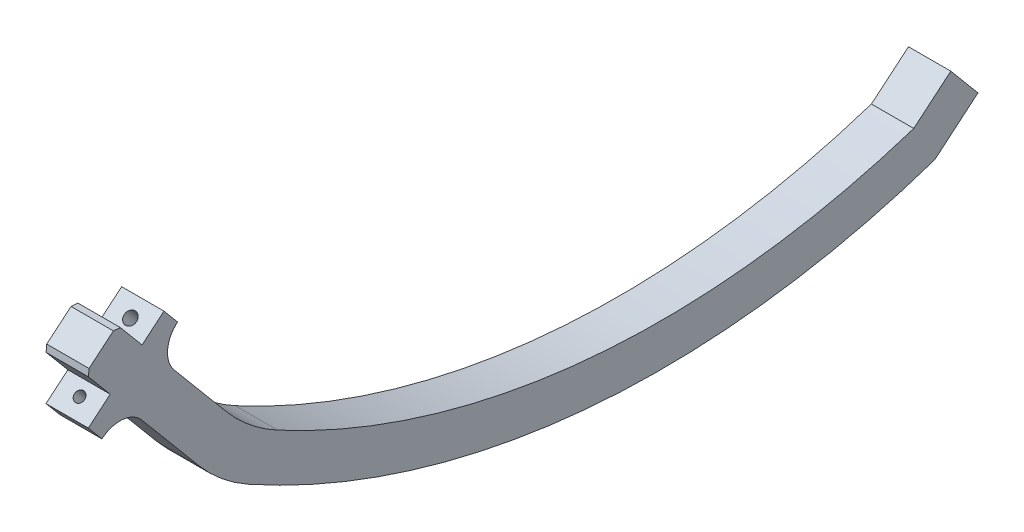
SolidWorks part; units mm, degrees
ref_plane "Ebene vorne" through (0, 0, 0) normal (0, 0, 1) x (1, 0, 0)
ref_plane "Ebene oben" through (0, 0, 0) normal (0, 1, 0) x (1, 0, 0)
ref_plane "Ebene rechts" through (0, 0, 0) normal (1, 0, 0) x (0, 0, -1)
sketch "Skizze1" plane through (0, 0, 0) normal (1, 0, 0) x (0, 0, -1)
  line L0 (0, 12) -> (-233.4212, 12) construction
  line L1 (-240, 65) -> (-230.7357, 72.7737)
  line L2 (0, 12) -> (-3.7358, 23.4037)
  line L3 (0, 12) -> (0, 39.1297) construction
  line L4 (0, 0) -> (-218.6687, 0) construction
  arc A0 (0, 12) -> (-240, 65) centre (-75.176, 241.4765) cw
  arc A1 (-3.7358, 23.4037) -> (-230.7357, 72.7737) centre (-75.176, 241.4765) cw
  dimension "D1" = 53
  dimension "D2" = 240
  dimension "D3" = 40
  dimension "D4" = 12
  dimension "D5" = 12
extrude "Aufsatz-Linear austragen1" add sketch "Skizze1" along normal blind 12
sketch "Skizze4" plane through (0, 0, 0) normal (1, 0, 0) x (0, 0, -1)
  line L0 (-230.7357, 72.7737) -> (-240, 65) construction
  line L2 (-3.7358, 23.4037) -> (6.769, 32.2183)
  line L3 (6.769, 32.2183) -> (14.4825, 23.0258)
  line L4 (14.4825, 23.0258) -> (2.2258, 12.7411)
  line L5 (-3.7358, 23.4037) -> (0, 12)
  arc A0 (0, 12) -> (2.2258, 12.7411) centre (-75.176, 241.4765) ccw
  arc A4 (-240, 65) -> (0, 12) centre (-75.176, 241.4765) ccw construction
  dimension "D1" = 16
  dimension "D2" = 12
extrude "Aufsatz-Linear austragen3" add sketch "Skizze4" along normal blind 12
sketch "Skizze5" plane through (12, 0, 0) normal (1, 0, 0) x (0, 0, -1)
  line L0 (-231.6625, 71.996) -> (-222.47, 79.7094)
  line L1 (-230.7357, 72.7737) -> (-232.109, 74.04) construction
  line L2 (-231.6625, 71.996) -> (-220.0923, 58.2072)
  line L3 (-230.7357, 72.7737) -> (-240, 65) construction
  line L4 (-222.47, 79.7094) -> (-210.8998, 65.9206)
  line L5 (-220.0923, 58.2072) -> (-192.9483, 44.5269)
  line L6 (-220.0923, 58.2072) -> (-211.3409, 65.5505) construction
  line L7 (-210.8998, 65.9206) -> (-192.9483, 44.5269)
  arc A6 (-230.7357, 72.7737) -> (-3.7358, 23.4037) centre (-75.176, 241.4765) ccw construction
  dimension "D1" = 12
  dimension "D2" = 1.2
  dimension "D3" = 18
extrude "Aufsatz-Linear austragen4" add sketch "Skizze5" against normal up to surface (12 mm away) up to face at (0, 27.4794, 77.4862)
sketch "Skizze6" plane through (12, 0, 0) normal (1, 0, 0) x (0, 0, -1)
  line L0 (-231.6625, 71.996) -> (-199.5106, 33.6789)
  line L1 (-199.5106, 33.6789) -> (-204.3677, 29.6033)
  line L2 (-204.3677, 29.6033) -> (-240, 65)
  line L3 (-240, 65) -> (-231.6625, 71.996)
extrude "Schnitt-Linear austragen1" cut sketch "Skizze6" against normal through all
sketch "Skizze7" plane through (12, 0, 0) normal (1, 0, 0) x (0, 0, -1)
  line L0 (-222.47, 79.7094) -> (-229.5406, 88.1359)
  line L1 (-192.9483, 44.5269) -> (-222.47, 79.7094) construction
  line L2 (-229.5406, 88.1359) -> (-238.7332, 80.4225)
  line L3 (-238.7332, 80.4225) -> (-231.6625, 71.996)
  line M4 (-222.47, 79.7094) -> (-231.6625, 71.996)
  dimension "D1" = 11
extrude "Aufsatz-Linear austragen5" [suppressed] add sketch "Skizze7" against normal up to surface (12 mm away) contours L2 L3 L0 M4
fillet "Verrundung1" radius 50 2 edges at (6, 35.2854, 200.8587) (6, 44.5269, 192.9483)
sketch "Skizze8" [suppressed] plane through (0, -76.6111, 91.3015) normal (0, 0.6428, -0.766) x (-1, 0, 0)
  line L0 (-6, 215.0619) -> (-6, 184.7045) construction
  line L1 (0, 215.0619) -> (-12, 215.0619) construction
  circle A0 centre (-6, 210.0619) radius 1.55
  dimension "D2" = 3.1
  dimension "D1" = 5
extrude "Schnitt-Linear austragen2" [suppressed] cut sketch "Skizze8" against normal blind 6
sketch "Skizze9" plane through (0, 156.3205, 131.1685) normal (0, 0.766, 0.6428) x (1, 0, 0)
  line L0 (6, -119.1857) -> (6, -131.1857) construction
  line L1 (0, -119.1857) -> (12, -119.1857) construction
  line L2 (0, -131.1857) -> (12, -131.1857) construction
  line L3 (12, -125.1857) -> (0, -125.1857) construction
  line L4 (12, -119.1857) -> (12, -131.1857) construction
  line L5 (0, -119.1857) -> (0, -131.1857) construction
  line L7 (0, -131.1857) -> (12, -131.1857)
  line L8 (0, -131.1857) -> (0, -119.1857)
  line L9 (0, -119.1857) -> (12, -119.1857)
  line L10 (12, -131.1857) -> (12, -119.1857)
  line L11 (0, -131.1857) -> (12, -119.1857) construction
  line L12 (0, -119.1857) -> (12, -131.1857) construction
  point P12 (6, -125.1857)
  dimension "D1" = 12
extrude "Aufsatz-Linear austragen6" add sketch "Skizze9" along normal blind 11
sketch "Skizze10" plane through (0, 0, 0) normal (-1, 0, 0) x (0, 0, 1)
  line L0 (231.6625, 71.996) -> (237.7909, 66.8537)
  line L1 (229.5406, 88.1359) -> (238.7332, 80.4225) construction
  line L2 (237.7909, 66.8537) -> (233.9341, 62.2574)
  line L3 (238.7332, 80.4225) -> (206.4468, 41.9451) construction
  line L4 (233.9341, 62.2574) -> (227.8058, 67.3997) construction
  line L5 (227.8058, 67.3997) -> (222.6635, 61.2714) construction
  line L6 (222.6635, 61.2714) -> (231.6625, 71.996)
  line L7 (234.1369, 84.2792) -> (238.5201, 89.5029) construction
  line L8 (218.6133, 75.1132) -> (213.471, 68.9848) construction
  line L9 (212.4849, 80.2555) -> (218.6133, 75.1132) construction
  line L10 (213.471, 68.9848) -> (222.47, 79.7094)
  line L11 (216.3416, 84.8517) -> (212.4849, 80.2555)
  line L12 (222.47, 79.7094) -> (216.3416, 84.8517)
  arc A0 (233.9341, 62.2574) -> (222.6635, 61.2714) centre (228.7918, 56.1291) ccw
  arc A1 (212.4849, 80.2555) -> (213.471, 68.9848) centre (207.3426, 74.1271) cw
  dimension "D1" = 6
  dimension "D2" = 8
  dimension "D3" = 11
extrude "Aufsatz-Linear austragen7" add sketch "Skizze10" against normal up to vertex (12 mm away) up to point (12, 41.9451, 206.4468)
sketch "Skizze11" plane through (0, 156.3205, 131.1685) normal (0, 0.766, 0.6428) x (1, 0, 0)
  line L0 (6, -119.1857) -> (6, -108.0662) construction
  line L1 (12, -119.1857) -> (0, -119.1857) construction
  line L2 (12, -125.1857) -> (20.5212, -125.1857) construction
  line L3 (12, -131.1857) -> (12, -119.1857) construction
  circle A0 centre (6, -115.7857) radius 1.75
  circle A1 centre (6, -134.5857) radius 1.45
  dimension "D1" = 3.5
  dimension "D2" = 3.4
  dimension "D3" = 2.9
extrude "Schnitt-Linear austragen3" cut sketch "Skizze11" against normal blind 10 contours A0 region at (6, 81.8949, 219.8654)
ref_plane "Ebene1" through (0, 148.6601, 124.7406) normal (0, 0.766, 0.6428) x (1, 0, 0)
sketch "Skizze12" plane through (0, 148.6601, 124.7406) normal (0, 0.766, 0.6428) x (1, 0, 0)
  line L0 (12, -125.1857) -> (17.337, -125.1857) construction
  line L1 (12, -131.1857) -> (12, -119.1857) construction
  circle A1 centre (6, -115.7857) radius 2.75
  dimension "D1" = 5.5
extrude "Schnitt-Linear austragen4" cut sketch "Skizze12" along normal blind 3.6
chamfer "Fase1" distance 1.5 angle 45 2 edges at (6, 88.1359, 229.5406) (6, 80.4225, 238.7332)
sketch "Skizze16" plane through (12, 0, 0) normal (1, 0, 0) x (0, 0, -1)
  line L0 (-222.47, 79.7094) -> (-222.5466, 79.6452)
  line L1 (-222.5466, 79.6452) -> (-228.7173, 86.9992)
  line L2 (-228.5765, 86.9869) -> (-230.6897, 87.1717) construction
  line L3 (-228.7173, 86.9992) -> (-228.6407, 87.0635)
  line L4 (-228.6407, 87.0635) -> (-222.47, 79.7094)
  line L5 (-222.47, 79.7094) -> (-228.5765, 86.9869) construction
  line L6 (-222.47, 79.7094) -> (-216.3416, 84.8517) construction
  line L7 (-234.1369, 84.2792) -> (-224.5632, 72.8697) construction
  line L8 (-237.5841, 81.3866) -> (-230.6897, 87.1717) construction
  line L9 (-237.8333, 79.35) -> (-231.6625, 71.996)
  line L10 (-237.7567, 79.4143) -> (-237.8333, 79.35)
  line L11 (-231.5859, 72.0603) -> (-237.7567, 79.4143)
  line L12 (-231.6625, 71.996) -> (-231.5859, 72.0603)
  dimension "D1" = 0.1
extrude "Schnitt-Linear austragen8" cut sketch "Skizze16" against normal through all
sketch "Skizze17" plane through (12, 0, 0) normal (1, 0, 0) x (0, 0, -1)
  line L0 (-223.0311, 45.9118) -> (-197.0813, 68.6509)
  line L1 (-197.0813, 68.6509) -> (28.1146, 79.9309)
  line L2 (28.1146, 79.9309) -> (56.5334, -12.5859)
  line L3 (56.5334, -12.5859) -> (-151.596, -41.8366)
  line L4 (-151.596, -41.8366) -> (-223.0311, 45.9118)
extrude "Schnitt-Linear austragen9" [suppressed] cut sketch "Skizze17" against normal through all
extrude "Schnitt-Linear austragen10" cut sketch "Skizze11<3>" against normal blind 6 contours A1 region at (6, 69.8105, 234.2671)
sketch "Skizze11<3>" plane through (0, 156.3205, 131.1685) normal (0, 0.766, 0.6428) x (1, 0, 0) same geometry as "Skizze11"
